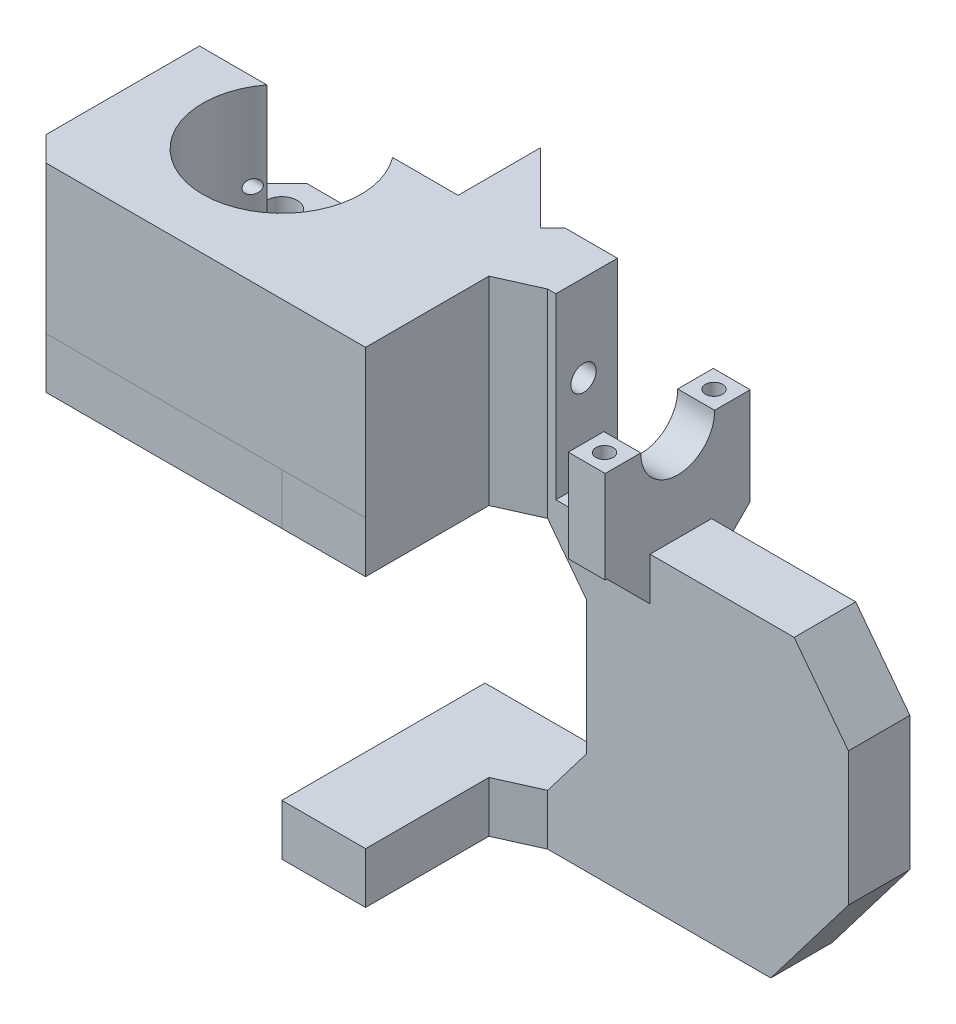
SolidWorks part; units mm, degrees
ref_plane "Přední rovina" through (0, 0, 0) normal (0, 0, 1) x (1, 0, 0)
ref_plane "Horní rovina" through (0, 0, 0) normal (0, 1, 0) x (1, 0, 0)
ref_plane "Pravá rovina" through (0, 0, 0) normal (1, 0, 0) x (0, 0, -1)
sketch "Skica1" plane through (0, 0, 0) normal (0, 0, 1) x (1, 0, 0)
  line L2 (15.4839, -19.9414) -> (15.4839, 1.7586)
  line L4 (58.0377, -19.9414) -> (58.0377, 1.7586)
  line L5 (-11, -36.4993) -> (-11, -28.2204)
  line L12 (58.0377, 1.7586) -> (45.4326, 18.3165)
  line L16 (15.4839, 1.7586) -> (9.1813, 10.0376)
  line L17 (45.4326, 18.3165) -> (2.8788, 18.3165)
  line L18 (9.1813, 10.0376) -> (-11, 10.0376)
  line L23 (2.8788, 18.3165) -> (-11, 18.3165)
  line L24 (-11, 10.0376) -> (-11, 18.3165)
  line L29 (45.2162, -9.0914) -> (58.0377, -9.0914) construction
  line L30 (9.1813, -28.2204) -> (-11, -28.2204)
  line L31 (15.4839, -19.9414) -> (9.1813, -28.2204)
  line L32 (45.4326, -36.4993) -> (2.8788, -36.4993)
  line L33 (58.0377, -19.9414) -> (45.4326, -36.4993)
  line L34 (2.8788, -36.4993) -> (-11, -36.4993)
  circle A2 centre (45.2162, -9.0914) radius 5.15
  circle A3 centre (24.2637, -9.0914) radius 5.15
  point P12 (-32.15, -1.7914)
extrude "Přidat vysunutím1" add sketch "Skica1" along normal blind 7 contours A2 L4 L12 L17 L34 L32 L33 L31 L30 L18 L16 L2 A3 region at (16.3654, -9.0914, 0)
sketch "Skica9" plane through (0, 0, 7) normal (0, 0, 1) x (1, 0, 0)
  line L12 (45.4326, -36.4993) -> (58.0377, -19.9414)
  line L13 (58.0377, -19.9414) -> (58.0377, 1.7586)
  line L14 (58.0377, 1.7586) -> (45.4326, 18.3165)
  line L15 (45.4326, 18.3165) -> (-11, 18.3165)
  line L16 (-11, 18.3165) -> (-11, 10.0376)
  line L17 (-11, 10.0376) -> (9.1813, 10.0376)
  line L18 (9.1813, 10.0376) -> (15.4839, 1.7586)
  line L19 (15.4839, 1.7586) -> (15.4839, -19.9414)
  line L20 (15.4839, -19.9414) -> (9.1813, -28.2204)
  line L21 (9.1813, -28.2204) -> (-11, -28.2204)
  line L22 (-11, -28.2204) -> (-11, -36.4993)
  line L23 (-11, -36.4993) -> (45.4326, -36.4993)
  line L24 (45.4326, -36.4993) -> (58.0377, -19.9414)
  line L25 (58.0377, -19.9414) -> (58.0377, 1.7586)
  line L26 (58.0377, 1.7586) -> (45.4326, 18.3165)
  line L27 (45.4326, 18.3165) -> (-11, 18.3165)
  line L28 (-11, 18.3165) -> (-11, 10.0376)
  line L29 (-11, 10.0376) -> (9.1813, 10.0376)
  line L30 (9.1813, 10.0376) -> (15.4839, 1.7586)
  line L31 (15.4839, 1.7586) -> (15.4839, -19.9414)
  line L32 (15.4839, -19.9414) -> (9.1813, -28.2204)
  line L33 (9.1813, -28.2204) -> (-11, -28.2204)
  line L34 (-11, -28.2204) -> (-11, -36.4993)
  line L35 (-11, -36.4993) -> (45.4326, -36.4993)
  dimension "D1" = 0
extrude "Přidat vysunutím6" add sketch "Skica9" along normal blind 1
sketch "Skica10" plane through (0, 0, 8) normal (0, 0, 1) x (1, 0, 0)
  line L1 (-11, -36.4993) -> (9.1813, -36.4993)
  line L2 (-11, -36.4993) -> (-11, -28.2204)
  line L3 (-11, -28.2204) -> (9.1813, -28.2204)
  line L4 (9.1813, -36.4993) -> (9.1813, -28.2204)
  line L5 (-11, 18.3165) -> (9.1813, 18.3165)
  line L6 (-11, 18.3165) -> (-11, 10.0376)
  line L7 (-11, 10.0376) -> (9.1813, 10.0376)
  line L8 (9.1813, 18.3165) -> (9.1813, 10.0376)
extrude "Přidat vysunutím7" add sketch "Skica10" along normal blind 23
sketch "Skica11" plane through (0, -36.4993, 0) normal (0, -1, 0) x (1, 0, 0)
  line L0 (9.1813, 8) -> (2.592, 10.9537)
  line L1 (2.592, 10.9537) -> (2.592, 31)
  line L2 (-11, 31) -> (9.1813, 31) construction
  line L3 (2.592, 31) -> (9.1813, 31)
  line L4 (9.1813, 31) -> (9.1813, 8)
extrude "Odebrat vysunutím3" cut sketch "Skica11" against normal up to surface (54.8159 mm away) up to face at (14.538, 18.3165, 13)
sketch "Skica12" plane through (0, 10.0376, 0) normal (0, -1, 0) x (1, 0, 0)
  line L0 (0, 0) -> (-11.2839, -11.2839)
  line L1 (-11.2839, -11.2839) -> (-49.3, -11.2839)
  line L2 (-49.3, -11.2839) -> (-53.3, -7.2839)
  line L3 (-53.3, -7.2839) -> (-53.3, 27.0161)
  line L4 (-53.3, 27.0161) -> (-49.3, 31.0161)
  line L5 (-49.3, 31.0161) -> (-11, 31)
  line L6 (-11, 31) -> (-11, 0)
  line L7 (-11, 0) -> (0, 0)
  circle A0 centre (-32.15, 9.8661) radius 12.8418
  circle A1 centre (-47.65, 25.3661) radius 1.6
  circle A2 centre (-16.65, 25.3661) radius 1.6
  circle A3 centre (-16.65, -5.6339) radius 1.6
  circle A4 centre (-47.65, -5.6339) radius 1.6
  dimension "D1" = 3.2
  dimension "D2" = 2
extrude "Přidat vysunutím8" add sketch "Skica12" against normal up to surface (8.279 mm away) up to face at (11.8901, 18.3165, 12.7077)
sketch "Skica13" plane through (0, 18.3165, 0) normal (0, 1, 0) x (1, 0, 0)
  circle A0 centre (-47.65, 5.6339) radius 2.5
  dimension "D1" = 5
extrude "Odebrat vysunutím4" cut sketch "Skica13" against normal blind 5
sketch "Skica14" plane through (0, 18.3165, 0) normal (0, 1, 0) x (1, 0, 0)
  line L0 (-42.3683, -2.0882) -> (-53.3, -2.0882)
  line L1 (-53.3, 7.2839) -> (-53.3, -27.0161) construction
  line L2 (-53.3, -2.0882) -> (-53.3, -27.0161)
  line L3 (-53.3, -27.0161) -> (-49.3, -31.0161)
  line L4 (-49.3, -31.0161) -> (2.592, -31)
  line L5 (2.592, -31) -> (2.592, -10.9537)
  line L6 (2.592, -10.9537) -> (2.592, -2.592)
  line L7 (2.592, -2.592) -> (-11.2839, 11.2839)
  line L8 (-11.2839, 11.2839) -> (-11.2839, -2.0882)
  line L9 (0, 0) -> (-11.2839, 11.2839) construction
  line L10 (-11.2839, -2.0882) -> (-21.9317, -2.0882)
  circle A0 centre (-32.15, -9.8661) radius 12.8418 construction
  arc A1 (-42.3683, -2.0882) -> (-21.9317, -2.0882) centre (-32.15, -9.8661) ccw
extrude "Přidat vysunutím9" add sketch "Skica14" along normal blind 22
sketch "Skica15" plane through (0, 0, 2.0882) normal (0, 0, -1) x (-1, 0, 0)
  line L0 (51.6, 36.8165) -> (46.7, 36.8165) construction
  line L1 (51.6, 21.8165) -> (46.7, 21.8165) construction
  circle A0 centre (49.15, 36.8165) radius 1.75
  circle A1 centre (49.15, 21.8165) radius 1.75
extrude "Odebrat vysunutím5" cut sketch "Skica15" against normal blind 22
sketch "Skica17" plane through (0, 0, 2.0882) normal (0, 0, -1) x (-1, 0, 0)
  line L0 (53.3, 40.3165) -> (53.3, 18.3165) construction
  point P0 (53.3, 36.8165)
  point P1 (53.3, 21.8165)
sketch "Skica18" plane through (-53.3, 0, 0) normal (-1, 0, 0) x (0, 0, 1)
  line L0 (2.0882, 36.8165) -> (27.0161, 36.8165) construction
  line L1 (27.0161, 40.3165) -> (27.0161, 10.0376) construction
  line L2 (2.0882, 21.8165) -> (27.0161, 21.8165) construction
  line L4 (16.0522, 39.8165) -> (13.0522, 39.8165)
  line L5 (16.0522, 39.8165) -> (16.0522, 33.8165)
  line L6 (16.0522, 33.8165) -> (13.0522, 33.8165)
  line L7 (13.0522, 39.8165) -> (13.0522, 33.8165)
  line L8 (16.0522, 39.8165) -> (13.0522, 33.8165) construction
  line L9 (16.0522, 33.8165) -> (13.0522, 39.8165) construction
  line L10 (16.0522, 24.8165) -> (13.0522, 24.8165)
  line L11 (16.0522, 24.8165) -> (16.0522, 18.8165)
  line L12 (16.0522, 18.8165) -> (13.0522, 18.8165)
  line L13 (13.0522, 24.8165) -> (13.0522, 18.8165)
  line L14 (16.0522, 24.8165) -> (13.0522, 18.8165) construction
  line L15 (16.0522, 18.8165) -> (13.0522, 24.8165) construction
  point P8 (14.5522, 36.8165)
  point P13 (14.5522, 21.8165)
  dimension "D1" = 6
  dimension "D2" = 3
extrude "Odebrat vysunutím6" cut sketch "Skica18" against normal blind 8
sketch "Skica19" plane through (0, 40.3165, 0) normal (0, 1, 0) x (1, 0, 0)
  line L8 (-42.3683, -2.0882) -> (-53.3, -2.0882)
  line L9 (-53.3, -2.0882) -> (-53.3, -27.0161)
  line L10 (-53.3, -27.0161) -> (-49.3, -31.0161)
  line L11 (-49.3, -31.0161) -> (2.592, -31)
  line L12 (2.592, -31) -> (2.592, -2.592)
  line L13 (2.592, -2.592) -> (-11.2839, 11.2839)
  line L14 (-11.2839, 11.2839) -> (-11.2839, -2.0882)
  line L15 (-11.2839, -2.0882) -> (-21.9317, -2.0882)
  line L16 (-42.3683, -2.0882) -> (-53.3, -2.0882)
  line L17 (-53.3, -2.0882) -> (-53.3, -27.0161)
  line L18 (-53.3, -27.0161) -> (-49.3, -31.0161)
  line L19 (-49.3, -31.0161) -> (2.592, -31)
  line L20 (2.592, -31) -> (2.592, -2.592)
  line L21 (2.592, -2.592) -> (-11.2839, 11.2839)
  line L22 (-11.2839, 11.2839) -> (-11.2839, -2.0882)
  line L23 (-11.2839, -2.0882) -> (-21.9317, -2.0882)
  arc A1 (-42.3683, -2.0882) -> (-21.9317, -2.0882) centre (-32.15, -9.8661) ccw
  arc A2 (-42.3683, -2.0882) -> (-21.9317, -2.0882) centre (-32.15, -9.8661) ccw
  dimension "D1" = 0
extrude "Přidat vysunutím10" add sketch "Skica19" along normal blind 2
ref_plane "Rovina2" through (-33.3, 0, 0) normal (-1, 0, 0) x (0, 0, 1)
sketch "Skica20" plane through (-33.3, 0, 0) normal (-1, 0, 0) x (0, 0, 1)
  circle A0 centre (3.507, 28.2297) radius 1.1
  point P2 (0, 0)
  point P3 (3.507, 28.2297)
  dimension "D1" = 2.2
extrude "Odebrat vysunutím7" cut sketch "Skica20" against normal mid plane 102
sketch "Skica21" plane through (2.592, 0, 0) normal (1, 0, 0) x (0, 0, -1)
  circle A0 centre (-3.507, 28.2297) radius 2.05
  dimension "D1" = 4.1
extrude "Odebrat vysunutím8" cut sketch "Skica21" against normal blind 30
sketch "Skica22" plane through (0, 0, 0) normal (0, 0, -1) x (-1, 0, 0)
  line L12 (-9.1813, 10.0376) -> (0, 10.0376)
  line L13 (0, 10.0376) -> (0, 18.3165)
  line L14 (0, 18.3165) -> (-45.4326, 18.3165)
  line L15 (-45.4326, 18.3165) -> (-58.0377, 1.7586)
  line L16 (-58.0377, 1.7586) -> (-58.0377, -19.9414)
  line L17 (-58.0377, -19.9414) -> (-45.4326, -36.4993)
  line L18 (-45.4326, -36.4993) -> (11, -36.4993)
  line L19 (11, -36.4993) -> (11, -28.2204)
  line L20 (11, -28.2204) -> (-9.1813, -28.2204)
  line L21 (-9.1813, -28.2204) -> (-15.4839, -19.9414)
  line L22 (-15.4839, -19.9414) -> (-15.4839, 1.7586)
  line L23 (-15.4839, 1.7586) -> (-9.1813, 10.0376)
  line L24 (-9.1813, 10.0376) -> (0, 10.0376)
  line L25 (0, 10.0376) -> (0, 18.3165)
  line L26 (0, 18.3165) -> (-45.4326, 18.3165)
  line L27 (-45.4326, 18.3165) -> (-58.0377, 1.7586)
  line L28 (-58.0377, 1.7586) -> (-58.0377, -19.9414)
  line L29 (-58.0377, -19.9414) -> (-45.4326, -36.4993)
  line L30 (-45.4326, -36.4993) -> (11, -36.4993)
  line L31 (11, -36.4993) -> (11, -28.2204)
  line L32 (11, -28.2204) -> (-9.1813, -28.2204)
  line L33 (-9.1813, -28.2204) -> (-15.4839, -19.9414)
  line L34 (-15.4839, -19.9414) -> (-15.4839, 1.7586)
  line L35 (-15.4839, 1.7586) -> (-9.1813, 10.0376)
  circle A0 centre (-45.2162, -9.0914) radius 5.15 construction
  circle A1 centre (-24.2637, -9.0914) radius 5.15 construction
  circle A2 centre (-45.2162, -9.0914) radius 5.15
  circle A3 centre (-24.2637, -9.0914) radius 5.15
  dimension "D1" = 0
extrude "Přidat vysunutím11" add sketch "Skica22" along normal blind 2
sketch "Skica23" plane through (0, 0, 7) normal (0, 0, -1) x (-1, 0, 0)
  circle A0 centre (-45.2162, -9.0914) radius 5.15 construction
  circle A1 centre (-24.2637, -9.0914) radius 5.15 construction
  circle A2 centre (-45.2162, -9.0914) radius 5.15
  circle A3 centre (-24.2637, -9.0914) radius 5.15
extrude "Přidat vysunutím12" add sketch "Skica23" along normal blind 2
chamfer "Zkosení1" distance 2 angle 45 1 edges at (0, 14.177, -2)
sketch "Skica24" plane through (0, 0, -2) normal (0, 0, -1) x (-1, 0, 0)
  line L1 (-57.1543, 13.3294) -> (-10.5103, 13.3294)
  line L2 (-57.1543, 13.3294) -> (-57.1543, 21.745)
  line L3 (-57.1543, 21.745) -> (-10.5103, 21.745)
  line L4 (-10.5103, 13.3294) -> (-10.5103, 21.745)
extrude "Odebrat vysunutím9" cut sketch "Skica24" against normal up to surface (10 mm away) up to face at (27.4633, -9.0914, 8)
sketch "Skica25" plane through (0, 18.3165, 0) normal (0, 1, 0) x (1, 0, 0)
  line L7 (9.1813, -8) -> (10.5103, -8)
  line L8 (10.5103, -8) -> (10.5103, 2)
  line L9 (10.5103, 2) -> (2, 2)
  line L10 (2, 2) -> (0, 0)
  line L11 (0, 0) -> (2.592, -2.592)
  line L12 (2.592, -2.592) -> (2.592, -10.9537)
  line L13 (2.592, -10.9537) -> (9.1813, -8)
  line L14 (9.1813, -8) -> (10.5103, -8)
  line L15 (10.5103, -8) -> (10.5103, 2)
  line L16 (10.5103, 2) -> (2, 2)
  line L17 (2, 2) -> (0, 0)
  line L18 (0, 0) -> (2.592, -2.592)
  line L19 (2.592, -2.592) -> (2.592, -10.9537)
  line L20 (2.592, -10.9537) -> (9.1813, -8)
  dimension "D1" = 0
extrude "Přidat vysunutím13" add sketch "Skica25" along normal up to surface (24 mm away) up to face at (-26.3982, 42.3165, 12.1459)
sketch "Skica26" plane through (0, 13.3294, 0) normal (0, 1, 0) x (1, 0, 0)
  line L1 (19.816, 8.2771) -> (25.816, 8.2771)
  line L2 (19.816, 8.2771) -> (19.816, -15.2912)
  line L3 (19.816, -15.2912) -> (25.816, -15.2912)
  line L4 (25.816, 8.2771) -> (25.816, -15.2912)
  line L5 (19.816, 8.2771) -> (25.816, -15.2912) construction
  line L6 (19.816, -15.2912) -> (25.816, 8.2771) construction
  point P0 (22.816, -3.507)
extrude "Přidat vysunutím14" add sketch "Skica26" along normal blind 15
sketch "Skica27" plane through (25.816, 0, 0) normal (1, 0, 0) x (0, 0, -1)
  circle A0 centre (-3.507, 28.2297) radius 6
extrude "Odebrat vysunutím10" cut sketch "Skica27" against normal blind 6
chamfer "Zkosení2" distance 7 angle 45 2 edges at (22.816, 13.3294, 8) (22.816, 13.3294, -2)
sketch "Skica28" plane through (0, 28.3294, 0) normal (0, 1, 0) x (1, 0, 0)
  circle A0 centre (22.816, -12.3987) radius 1.4
  circle A1 centre (22.816, 5.3846) radius 1.4
  dimension "D1" = 2.8
extrude "Odebrat vysunutím11" cut sketch "Skica28" against normal blind 10
sketch "Skica29" plane through (2.592, 0, 0) normal (-1, 0, 0) x (0, 0, 1)
  circle A0 centre (3.507, 28.2297) radius 2.05
extrude "Odebrat vysunutím12" cut sketch "Skica29" against normal blind 10
